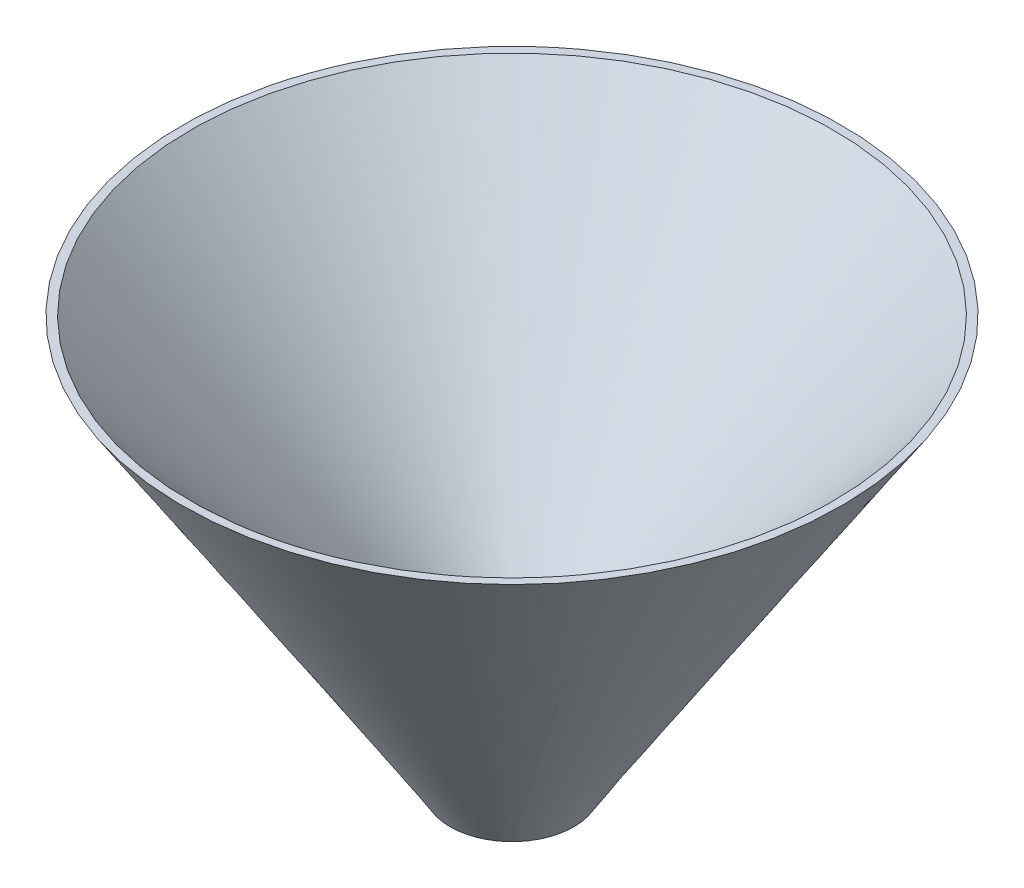
SolidWorks part; units mm, degrees
ref_plane "Front Plane" through (0, 0, 0) normal (0, 0, 1) x (1, 0, 0)
ref_plane "Top Plane" through (0, 0, 0) normal (0, 1, 0) x (1, 0, 0)
ref_plane "Right Plane" through (0, 0, 0) normal (1, 0, 0) x (0, 0, -1)
sketch "Sketch1" plane through (0, 0, 0) normal (0, 1, 0) x (1, 0, 0)
  circle A0 centre (0, 0) radius 7.5
ref_plane "Plane2" through (0, 50, 0) normal (0, 1, 0) x (1, 0, 0)
sketch "Sketch2" plane through (0, 50, 0) normal (0, 1, 0) x (1, 0, 0)
  circle A0 centre (0, 0) radius 40
  dimension "D1" = 80
loft "Loft1" add profiles "Sketch1", "Sketch2" connector at (5.0196, 0, 5.5725) connector at (33.3215, 50, 22.1287)
sketch "Sketch3" plane through (0, 0, 0) normal (0, 1, 0) x (1, 0, 0)
  circle A0 centre (0, 0) radius 7
sketch "Sketch4" plane through (0, 50, 0) normal (0, 1, 0) x (1, 0, 0)
  circle A0 centre (0, 0) radius 39
  dimension "D1" = 78
loft "Cut-Loft1" cut profiles "Sketch4", "Sketch3" connector at (-20.0211, 50, -33.4687) connector at (6.419, 0, 2.7921)
